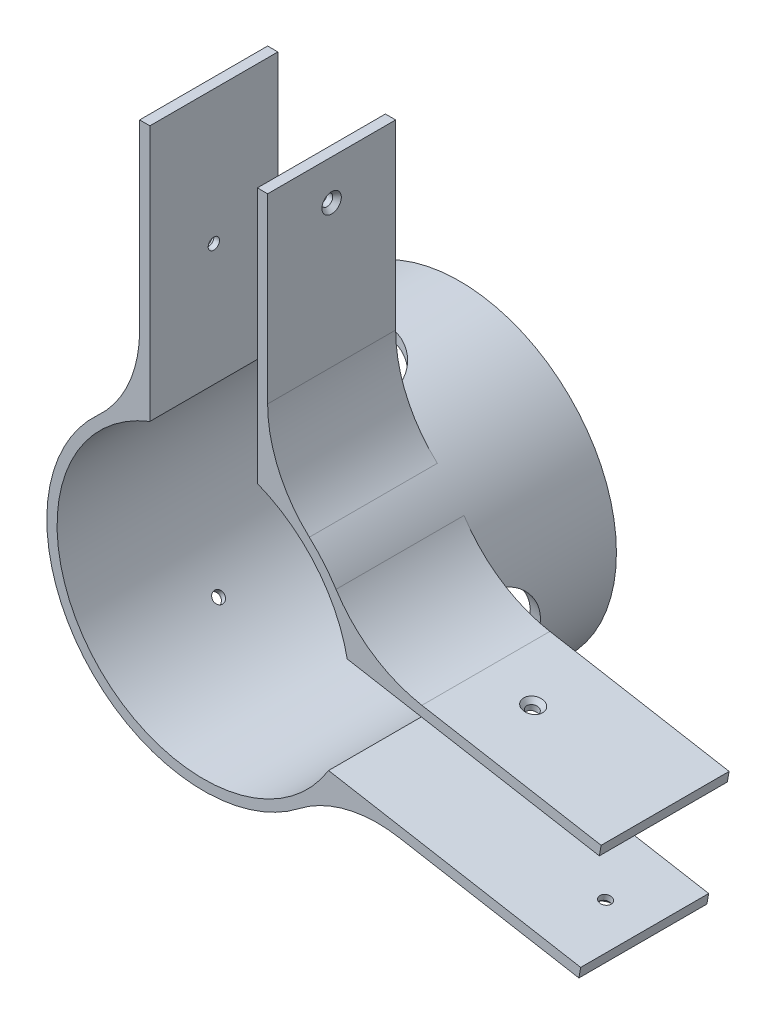
SolidWorks part; units mm, degrees
ref_plane "Plan de face" through (0, 0, 0) normal (0, 0, 1) x (1, 0, 0)
ref_plane "Plan de dessus" through (0, 0, 0) normal (0, 1, 0) x (1, 0, 0)
ref_plane "Plan de droite" through (0, 0, 0) normal (1, 0, 0) x (0, 0, -1)
sketch "Esquisse1" plane through (0, 0, 0) normal (0, 0, 1) x (1, 0, 0)
  line L0 (0, 0) -> (0, 24.5) construction
  line L1 (0, 0) -> (22.5521, -3.9765) construction
  circle A0 centre (0, 0) radius 22.9
  circle A1 centre (0, 0) radius 24.5
  dimension "D1" = 45.8
  dimension "D3" = 100
  dimension "D2" = 1.6
extrude "Boss.-Extru.1" add sketch "Esquisse1" along normal blind 40
sketch "Esquisse2" plane through (0, 0, 0) normal (0, 1, 0) x (1, 0, 0)
  line L1 (-24.5, -40) -> (24.5, -40) construction
  line L2 (-8.4, -40) -> (-8.4, -20)
  line L3 (8.4, -20) -> (8.4, -40)
  line L6 (-8.4, -40) -> (8.4, -40)
  arc A0 (-8.4, -20) -> (8.4, -20) centre (0, -20) cw
  dimension "D1" = 16.8
  dimension "D2" = 20
extrude "Enlèv. mat.-Extru.1" cut sketch "Esquisse2" along normal through all
sketch "Esquisse3" plane through (-8.4, 0, 0) normal (1, 0, 0) x (0, 0, -1)
  line L0 (-20, 21.3038) -> (-40, 21.3038)
  line L1 (-20, 21.3038) -> (-20, 61.3038)
  line L2 (-40, 21.3038) -> (-40, 61.3038)
  line L3 (-20, 61.3038) -> (-40, 61.3038)
  dimension "D1" = 40
extrude "Boss.-Extru.2" add sketch "Esquisse3" against normal blind 1.6
sketch "Esquisse4" plane through (8.4, 0, 0) normal (-1, 0, 0) x (0, 0, 1)
  line L0 (40, 21.3038) -> (20, 21.3038)
  line L1 (40, 21.3038) -> (40, 61.3038)
  line L2 (20, 21.3038) -> (20, 61.3038)
  line L3 (40, 61.3038) -> (20, 61.3038)
  dimension "D1" = 40
extrude "Boss.-Extru.3" add sketch "Esquisse4" against normal blind 1.6
fillet "Congé1" radius 20 2 edges at (-10, 22.3663, 30) (10, 22.3663, 30)
hole_wizard "Fraisage pour vis à tête fraisée bombée #01" positions "Esquisse5" profile "Esquisse6" countersink size "#0" standard "Ansi Inch" end condition up to next
sketch "Esquisse5" plane through (10, 0, 0) normal (1, 0, 0) x (0, 0, -1)
  point P0 (-30, 55.0892)
  point P1 (-30, 55.0892)
sketch "Esquisse6" plane through (10, 55.0892, 30) normal (0, 1, 0) x (0, 0, -1)
  line L0 (0, 0) -> (0, 1.6)
  line L1 (0, 1.6) -> (0.889, 1.6)
  line L2 (0.889, 1.6) -> (0.889, 0.7159)
  line L3 (0.889, 0.7159) -> (1.5113, 0)
  line L5 (1.5113, 0) -> (0, 0)
  line L6 (-0.889, 0.7159) -> (-1.5113, 0) construction
  line L11 (0, -6.35) -> (0, 107.95) construction
  dimension "Diamètre du perçage jusqu'au prochain" = 1.778
  dimension "Profondeur du perçage jusqu'au prochain" = 1.6
  dimension "Diamètre du fraisage entrant" = 3.0226
  dimension "Angle du fraisage entrant" = 82
hole_wizard "Fraisage pour vis à tête fraisée bombée #02" positions "Esquisse7" profile "Esquisse8" countersink size "#0" standard "Ansi Inch" end condition up to next
sketch "Esquisse7" plane through (-10, 0, 0) normal (-1, 0, 0) x (0, 0, 1)
  point P0 (30, 40.3697)
  point P2 (30, 40.3697)
sketch "Esquisse8" plane through (-10, 40.3697, 30) normal (0, 1, 0) x (0, 0, 1)
  line L0 (0, 0) -> (0, 1.6)
  line L1 (0, 1.6) -> (0.889, 1.6)
  line L2 (0.889, 1.6) -> (0.889, 0.7159)
  line L3 (0.889, 0.7159) -> (1.5113, 0)
  line L5 (1.5113, 0) -> (0, 0)
  line L6 (-0.889, 0.7159) -> (-1.5113, 0) construction
  line L11 (0, -6.35) -> (0, 107.95) construction
  dimension "Diamètre du perçage jusqu'au prochain" = 1.778
  dimension "Profondeur du perçage jusqu'au prochain" = 1.6
  dimension "Diamètre du fraisage entrant" = 3.0226
  dimension "Angle du fraisage entrant" = 82
pattern_circular "Répétition circulaire1" count 2 over 100 about axis through (0, 0, 0) along (0, 0, 1) of "Enlèv. mat.-Extru.1", "Boss.-Extru.2", "Boss.-Extru.3", "Fraisage pour vis à tête fraisée bombée #01", "Fraisage pour vis à tête fraisée bombée #02", "Congé1" reverse direction yes
hole_wizard "Fraisage pour vis à tête fraisée bombée #03" positions "Esquisse3D1" profile "Esquisse9" countersink size "#0" standard "Ansi Inch" end condition up to next
sketch3d "Esquisse3D1"
  point P0 (-17.6181, -17.0251, 21.2022)
sketch "Esquisse9" plane through (-17.6181, -17.0251, 21.2022) normal (0, 0, 1) x (0.6949, -0.7191, 0)
  line L0 (0, 0) -> (0, 1.6)
  line L1 (0, 1.6) -> (0.889, 1.6)
  line L2 (0.889, 1.6) -> (0.889, 0.7159)
  line L3 (0.889, 0.7159) -> (1.5113, 0)
  line L5 (1.5113, 0) -> (0, 0)
  line L6 (-0.889, 0.7159) -> (-1.5113, 0) construction
  line L11 (0, -6.35) -> (0, 107.95) construction
  dimension "Diamètre du perçage jusqu'au prochain" = 1.778
  dimension "Profondeur du perçage jusqu'au prochain" = 1.6
  dimension "Diamètre du fraisage entrant" = 3.0226
  dimension "Angle du fraisage entrant" = 82
